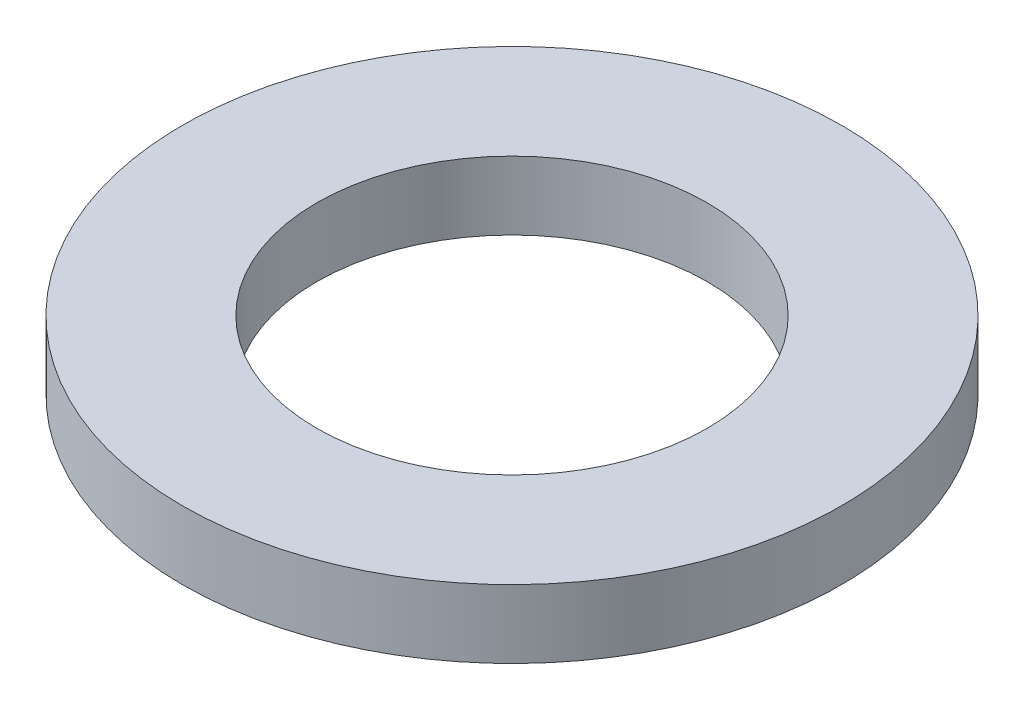
SolidWorks part; units mm, degrees
ref_plane "Front Plane" through (0, 0, 0) normal (0, 0, 1) x (1, 0, 0)
ref_plane "Top Plane" through (0, 0, 0) normal (0, 1, 0) x (1, 0, 0)
ref_plane "Right Plane" through (0, 0, 0) normal (1, 0, 0) x (0, 0, -1)
sketch "Sketch1" plane through (0, 0, 0) normal (0, 1, 0) x (1, 0, 0)
  circle A0 centre (0, 0) radius 67.5
  dimension "FLANGE_OD" = 135
extrude "Boss-Extrude1" add sketch "Sketch1" along normal blind 14
sketch "Sketch2" plane through (0, 0, 0) normal (0, 1, 0) x (1, 0, 0)
  circle A0 centre (0, 0) radius 40
  dimension "BORE_D" = 80
extrude "Cut-Extrude1" cut sketch "Sketch2" along normal through all
sketch "Sketch3" plane through (0, 14, 0) normal (0, 1, 0) x (1, 0, 0)
  circle A0 centre (0, 0) radius 25.5632 construction
  circle A1 centre (-25.5632, 0) radius 1.8028
  dimension "BOLT_D" = 3.6056
  dimension "BOLT_PCD" = 51.1264
extrude "Cut-Extrude2" cut sketch "Sketch3" against normal blind 11.4772 rebuild error yes
pattern_circular "CirPattern1" count 3 over 360 rebuild error yes
